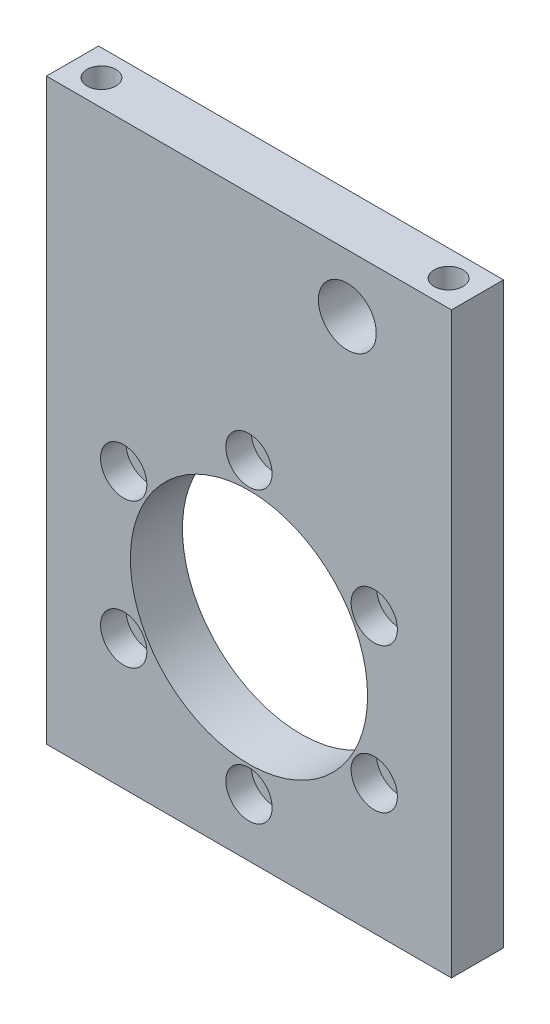
SolidWorks part; units mm, degrees
material "1060 Alloy"
ref_plane "Front Plane" through (0, 0, 0) normal (0, 0, 1) x (1, 0, 0)
ref_plane "Top Plane" through (0, 0, 0) normal (0, 1, 0) x (1, 0, 0)
ref_plane "Right Plane" through (0, 0, 0) normal (1, 0, 0) x (0, 0, -1)
sketch "Sketch1" plane through (0, 0, 0) normal (0, 0, 1) x (1, 0, 0)
  line L1 (0, 0) -> (70, 0)
  line L2 (0, 0) -> (0, 100)
  line L3 (0, 100) -> (70, 100)
  line L4 (70, 0) -> (70, 100)
  dimension "D1" = 70
  dimension "D2" = 100
extrude "Boss-Extrude1" add sketch "Sketch1" along normal mid plane 9
sketch "Sketch3" plane through (0, 0, 0) normal (0, 0, 1) x (1, 0, 0)
  circle A0 centre (35, 35) radius 20.5
  dimension "D1" = 41
  dimension "D2" = 35
  dimension "D3" = 35
extrude "Cut-Extrude2" cut sketch "Sketch3" against normal through all both and the other way through all
hole_wizard "M6 Tapped Hole1" positions "Sketch4" profile "Sketch5" tap size "M6" standard "ISO"
sketch "Sketch4" plane through (0, 0, 0) normal (0, -1, 0) x (-1, 0, 0)
  line L0 (-70, -4.5) -> (-70, 4.5) construction
  line L1 (0, -4.5) -> (0, 4.5) construction
  point P0 (-65, 0)
  point P2 (-5, 0)
  dimension "D1" = 5
  dimension "D2" = 5
sketch "Sketch5" plane through (65, 0, 0) normal (1, 0, 0) x (0, 0, -1)
  line L0 (0, 0) -> (0, 16.5022)
  line L1 (0, 16.5022) -> (2.5, 15)
  line L2 (2.5, 15) -> (2.5, 0)
  line L5 (2.5, 0) -> (0, 0)
  line L10 (0, 16.5022) -> (-2.5, 15) construction
  line L11 (0, -6.35) -> (0, 107.95) construction
  dimension "Tap Drill Dia." = 5
  dimension "Tap Drill Depth" = 15
  dimension "Drill Angle" = 118
cosmetic thread "Hole Thread1" parameters "D1"=12, "D2"=6
cosmetic thread "Hole Thread2" parameters "D1"=12, "D2"=6
ref_plane "Plane1" through (0, 50, 0) normal (0, 1, 0) x (1, 0, 0)
mirror "Mirror1" about plane through (0, 50, 0) normal (0, 1, 0) of "M6 Tapped Hole1"
hole_wizard "CBORE for M4 Hex Socket Head Cap Screw1" positions "Sketch6" profile "Sketch7" counterbore size "M4" standard "ISO" end condition through all
sketch "Sketch6" plane through (0, 0, 4.5) normal (0, 0, 1) x (1, 0, 0)
  line L0 (14.5, 35) -> (55.5, 35) construction
  circle A0 centre (35, 35) radius 20.5 construction
  point P0 (35, 60)
  point P16 (35, 35)
  dimension "D1" = 25
sketch "Sketch7" plane through (35, 60, 4.5) normal (1, 0, 0) x (0, -1, 0)
  line L0 (0, 0) -> (0, 9)
  line L1 (0, 9) -> (2.15, 9)
  line L3 (2.15, 9) -> (2.15, 4.4)
  line L4 (2.15, 4.4) -> (4, 4.4)
  line L5 (4, 4.4) -> (4, 0)
  line L7 (4, 0) -> (0, 0)
  line L11 (0, -6.35) -> (0, 107.95) construction
  dimension "Thru Hole Dia." = 4.3
  dimension "Thru Hole Depth" = 9
  dimension "C'Bore Dia." = 8
  dimension "C'Bore Depth" = 4.4
pattern_circular "CirPattern1" count 6 over 360 about axis through (35, 35, -4.5) along (0, 0, 1) of "CBORE for M4 Hex Socket Head Cap Screw1"
sketch "Sketch8" plane through (0, 0, 4.5) normal (0, 0, 1) x (1, 0, 0)
  line L0 (70, 100) -> (0, 100) construction
  line L1 (70, 0) -> (70, 100) construction
  circle A0 centre (52, 90) radius 5
  dimension "D1" = 10
  dimension "D2" = 10
  dimension "D3" = 18
extrude "Cut-Extrude3" cut sketch "Sketch8" against normal blind 10
move or copy body "Body-Move/Copy1" [suppressed] bodies to move or copy 111
